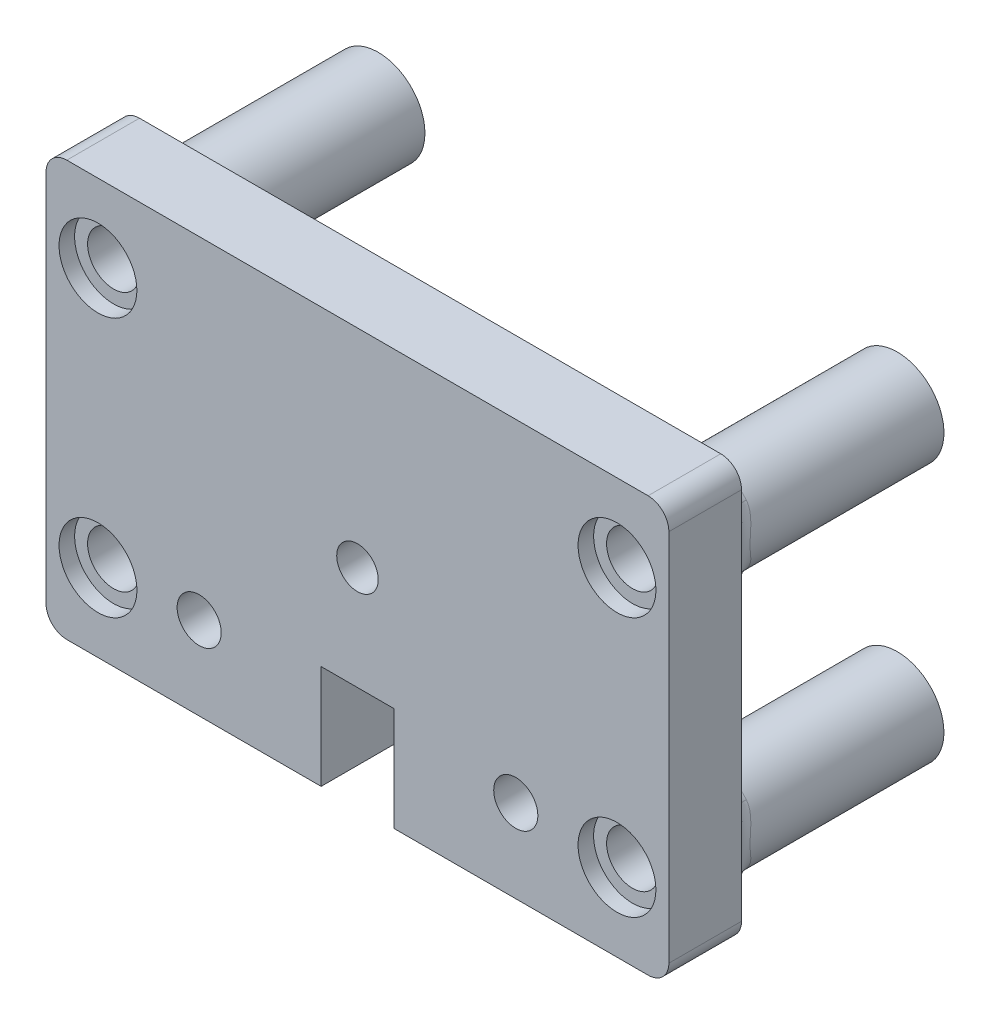
SolidWorks part; units mm, degrees
ref_plane "Plan de face" through (0, 0, 0) normal (0, 0, 1) x (1, 0, 0)
ref_plane "Plan de dessus" through (0, 0, 0) normal (0, 1, 0) x (1, 0, 0)
ref_plane "Plan de droite" through (0, 0, 0) normal (1, 0, 0) x (0, 0, -1)
sketch "Esquisse1" plane through (0, 0, 0) normal (0, 0, 1) x (1, 0, 0)
  line L1 (0, 0) -> (60, 0)
  line L2 (0, 0) -> (0, -40)
  line L3 (0, -40) -> (60, -40)
  line L4 (60, 0) -> (60, -40)
  dimension "D1" = 40
  dimension "D2" = 60
extrude "Boss.-Extru.1" add sketch "Esquisse1" along normal blind 7
fillet "Congé1" radius 2 4 edges at (0, -40, 3.5) (0, 0, 3.5) (60, 0, 3.5) (60, -40, 3.5)
sketch "Esquisse2" plane through (0, 0, 0) normal (0, 0, -1) x (-1, 0, 0)
  circle A0 centre (-30, -20) radius 2
  dimension "D1" = 4
extrude "Enlèv. mat.-Extru.1" cut sketch "Esquisse2" against normal through all
sketch "Esquisse3" plane through (0, 0, 0) normal (0, 0, -1) x (-1, 0, 0)
  line L0 (-30, -40) -> (-30, 0) construction
  line L1 (-2, -40) -> (-58, -40) construction
  line L2 (-58, 0) -> (-2, 0) construction
  line L3 (0, -20) -> (-60, -20) construction
  line L4 (0, -2) -> (0, -38) construction
  line L5 (-60, -38) -> (-60, -2) construction
  circle A0 centre (-5, -32.5) radius 2.5
  circle A1 centre (-5, -32.5) radius 4.5
  circle A2 centre (-5, -7.5) radius 4.5
  circle A3 centre (-5, -7.5) radius 2.5
  circle A4 centre (-55, -7.5) radius 2.5
  circle A5 centre (-55, -7.5) radius 4.5
  circle A6 centre (-55, -32.5) radius 4.5
  circle A7 centre (-55, -32.5) radius 2.5
  dimension "D1" = 5
  dimension "D4" = 9
  dimension "D2" = 12.5
  dimension "D3" = 25
extrude "Boss.-Extru.2" add sketch "Esquisse3" along normal blind 20
fillet "Congé2" radius 2 4 edges at (9.5, -7.5, 0) (59.5, -7.5, 0) (59.5, -32.5, 0) (9.5, -32.5, 0)
sketch "Esquisse4" plane through (0, 0, 0) normal (0, 0, -1) x (-1, 0, 0)
  circle A0 centre (-55, -32.5) radius 2.5
  circle A1 centre (-55, -7.5) radius 2.5
  circle A2 centre (-5, -7.5) radius 2.5
  circle A3 centre (-5, -32.5) radius 2.5
extrude "Enlèv. mat.-Extru.2" cut sketch "Esquisse4" against normal through all
sketch "Esquisse5" plane through (0, 0, 7) normal (0, 0, 1) x (1, 0, 0)
  line L0 (0, -20) -> (60, -20) construction
  line L1 (0, -2) -> (0, -38) construction
  line L2 (60, -38) -> (60, -2) construction
  line L3 (30, 0) -> (30, -40) construction
  line L4 (58, 0) -> (2, 0) construction
  line L5 (2, -40) -> (58, -40) construction
  circle A0 centre (55, -32.5) radius 3.75
  circle A1 centre (55, -7.5) radius 3.75
  circle A2 centre (5, -7.5) radius 3.75
  circle A3 centre (5, -32.5) radius 3.75
  dimension "D1" = 7.5
extrude "Enlèv. mat.-Extru.3" cut sketch "Esquisse5" against normal blind 1.5
sketch "Esquisse6" plane through (0, 0, 7) normal (0, 0, 1) x (1, 0, 0)
  line L0 (30, -20) -> (30, -40) construction
  line L1 (2, -40) -> (58, -40) construction
  line L3 (26.5, -30) -> (33.5, -30)
  line L4 (26.5, -30) -> (26.5, -40)
  line L5 (26.5, -40) -> (33.5, -40)
  line L6 (33.5, -30) -> (33.5, -40)
  dimension "D1" = 7
  dimension "D2" = 10
extrude "Enlèv. mat.-Extru.4" cut sketch "Esquisse6" against normal through all
sketch "Esquisse7" plane through (0, 0, 7) normal (0, 0, 1) x (1, 0, 0)
  line L0 (30, 0) -> (30, -40.0956) construction
  line L1 (58, 0) -> (2, 0) construction
  line L2 (2, -40) -> (26.5, -40) construction
  circle A0 centre (14.75, -32) radius 2.125
  circle A1 centre (45.25, -32) radius 2.125
  dimension "D1" = 4.25
  dimension "D3" = 8
  dimension "D2" = 15.25
extrude "Enlèv. mat.-Extru.5" cut sketch "Esquisse7" against normal through all
sketch "Esquisse8" plane through (0, 0, 0) normal (0, 0, -1) x (-1, 0, 0)
  circle A0 centre (-14.75, -32) radius 4
  circle A1 centre (-45.25, -32) radius 4
  dimension "D1" = 8
  dimension "D2" = 8
extrude "Enlèv. mat.-Extru.6" cut sketch "Esquisse8" against normal blind 3
